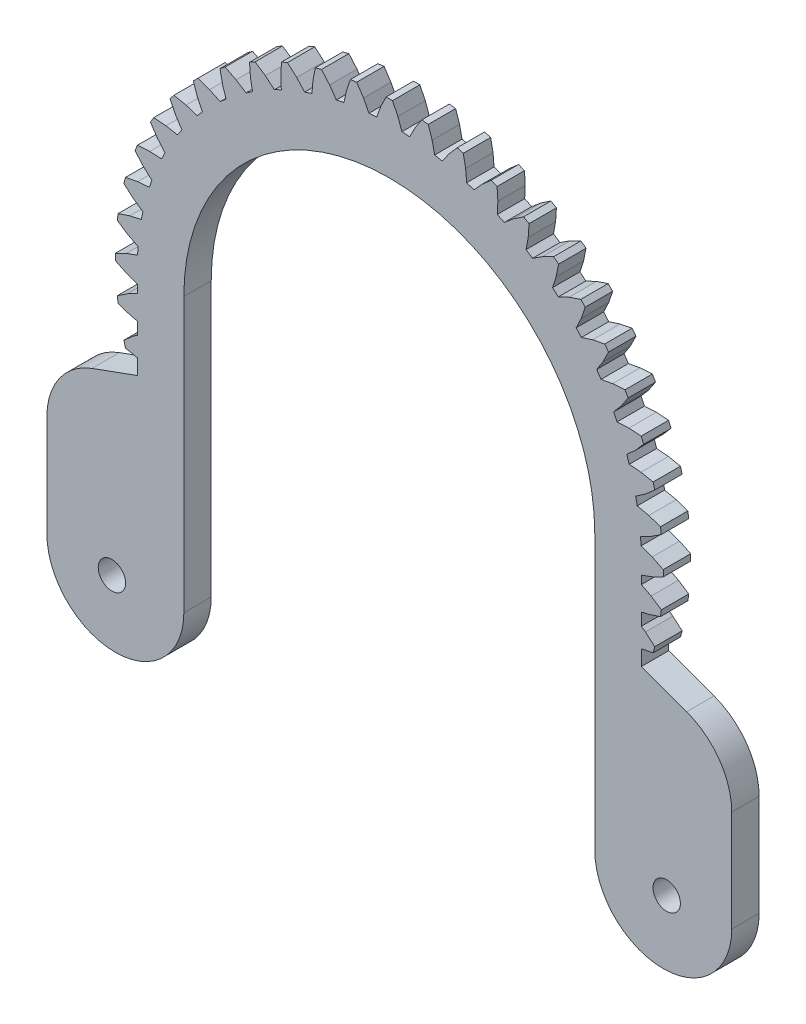
SolidWorks part; units mm, degrees
material "Delrin 2700 NC010, Low Viscosity Acetal Copolymer (SS)"
ref_plane "Front Plane" through (0, 0, 0) normal (0, 0, 1) x (1, 0, 0)
ref_plane "Top Plane" through (0, 0, 0) normal (0, 1, 0) x (1, 0, 0)
ref_plane "Right Plane" through (0, 0, 0) normal (1, 0, 0) x (0, 0, -1)
sketch "Sketch1" plane through (0, 0, 0) normal (0, 0, 1) x (1, 0, 0)
  line L0 (83.8835, 67.191) -> (85.5092, 66.6061)
  line L1 (85.5092, 66.6061) -> (87.1271, 65.8138)
  line L2 (87.1271, 65.8138) -> (87.1271, 64.8854)
  line L3 (87.1271, 64.8854) -> (85.5092, 64.0931)
  line L4 (85.5092, 64.0931) -> (83.8835, 63.5083)
  line L5 (83.8835, 63.5083) -> (83.8095, 62.3776)
  line L6 (83.8095, 62.3776) -> (85.3448, 61.5855)
  line L7 (85.3448, 61.5855) -> (86.8456, 60.5888)
  line L8 (86.8456, 60.5888) -> (86.7243, 59.6683)
  line L9 (86.7243, 59.6683) -> (85.0168, 59.094)
  line L10 (85.0168, 59.094) -> (83.3288, 58.7263)
  line L11 (83.3288, 58.7263) -> (83.1077, 57.615)
  line L12 (83.1077, 57.615) -> (84.5266, 56.6293)
  line L13 (84.5266, 56.6293) -> (85.8844, 55.4453)
  line L14 (85.8844, 55.4453) -> (85.6441, 54.5485)
  line L15 (85.6441, 54.5485) -> (83.8761, 54.202)
  line L16 (83.8761, 54.202) -> (82.1545, 54.0577)
  line L17 (82.1545, 54.0577) -> (81.7903, 52.9848)
  line L18 (81.7903, 52.9848) -> (83.0684, 51.8222)
  line L19 (83.0684, 51.8222) -> (84.26, 50.4711)
  line L20 (84.26, 50.4711) -> (83.9048, 49.6134)
  line L21 (83.9048, 49.6134) -> (82.1066, 49.5006)
  line L22 (82.1066, 49.5006) -> (80.3809, 49.5823)
  line L23 (80.3809, 49.5823) -> (79.8799, 48.5661)
  line L24 (79.8799, 48.5661) -> (80.9952, 47.2468)
  line L25 (80.9952, 47.2468) -> (82.0003, 45.7516)
  line L26 (82.0003, 45.7516) -> (81.5361, 44.9476)
  line L27 (81.5361, 44.9476) -> (79.7387, 45.0704)
  line L28 (79.7387, 45.0704) -> (78.0384, 45.3766)
  line L29 (78.0384, 45.3766) -> (77.4089, 44.4346)
  line L30 (77.4089, 44.4346) -> (78.3426, 42.9809)
  line L31 (78.3426, 42.9809) -> (79.1439, 41.3674)
  line L32 (79.1439, 41.3674) -> (78.5788, 40.6309)
  line L33 (78.5788, 40.6309) -> (76.8128, 40.9873)
  line L34 (76.8128, 40.9873) -> (75.167, 41.5128)
  line L35 (75.167, 41.5128) -> (74.4199, 40.6609)
  line L36 (74.4199, 40.6609) -> (75.1558, 39.0979)
  line L37 (75.1558, 39.0979) -> (75.7397, 37.3936)
  line L38 (75.7397, 37.3936) -> (75.0832, 36.737)
  line L39 (75.0832, 36.737) -> (73.3788, 37.3209)
  line L40 (73.3788, 37.3209) -> (71.8158, 38.0569)
  line L41 (71.8158, 38.0569) -> (70.9639, 37.3097)
  line L42 (70.9639, 37.3097) -> (71.4895, 35.6639)
  line L43 (71.4895, 35.6639) -> (71.8459, 33.898)
  line L44 (71.8459, 33.898) -> (71.1093, 33.3328)
  line L45 (71.1093, 33.3328) -> (69.4958, 34.1341)
  line L46 (69.4958, 34.1341) -> (68.0421, 35.0679)
  line L47 (68.0421, 35.0679) -> (67.1001, 34.4384)
  line L48 (67.1001, 34.4384) -> (67.4064, 32.738)
  line L49 (67.4064, 32.738) -> (67.5292, 30.9407)
  line L50 (67.5292, 30.9407) -> (66.7251, 30.4764)
  line L51 (66.7251, 30.4764) -> (65.23, 31.4815)
  line L52 (65.23, 31.4815) -> (63.9107, 32.5969)
  line L53 (63.9107, 32.5969) -> (62.8945, 32.0958)
  line L54 (62.8945, 32.0958) -> (62.9762, 30.3701)
  line L55 (62.9762, 30.3701) -> (62.8633, 28.572)
  line L56 (62.8633, 28.572) -> (62.0056, 28.2167)
  line L57 (62.0056, 28.2167) -> (60.6545, 29.4083)
  line L58 (60.6545, 29.4083) -> (59.4919, 30.6864)
  line L59 (59.4919, 30.6864) -> (58.419, 30.3222)
  line L60 (58.419, 30.3222) -> (58.2748, 28.6006)
  line L61 (58.2748, 28.6006) -> (57.9283, 26.8327)
  line L62 (57.9283, 26.8327) -> (57.0315, 26.5924)
  line L63 (57.0315, 26.5924) -> (55.8474, 27.9502)
  line L64 (55.8474, 27.9502) -> (54.8618, 29.369)
  line L65 (54.8618, 29.369) -> (53.7504, 29.1479)
  line L66 (53.7504, 29.1479) -> (53.3827, 27.4599)
  line L67 (53.3827, 27.4599) -> (52.8084, 25.7524)
  line L68 (52.8084, 25.7524) -> (51.888, 25.6311)
  line L69 (51.888, 25.6311) -> (50.8913, 27.1319)
  line L70 (50.8913, 27.1319) -> (50.0992, 28.6672)
  line L71 (50.0992, 28.6672) -> (48.9685, 28.5932)
  line L72 (48.9685, 28.5932) -> (48.3836, 26.9675)
  line L73 (48.3836, 26.9675) -> (47.5914, 25.3496)
  line L74 (47.5914, 25.3496) -> (46.6629, 25.3496)
  line L75 (46.6629, 25.3496) -> (45.8707, 26.9675)
  line L76 (45.8707, 26.9675) -> (45.2858, 28.5932)
  line L77 (45.2858, 28.5932) -> (44.1551, 28.6672)
  line L78 (44.1551, 28.6672) -> (43.363, 27.1319)
  line L79 (43.363, 27.1319) -> (42.3663, 25.6311)
  line L80 (42.3663, 25.6311) -> (41.4459, 25.7524)
  line L81 (41.4459, 25.7524) -> (40.8715, 27.4599)
  line L82 (40.8715, 27.4599) -> (40.5038, 29.1479)
  line L83 (40.5038, 29.1479) -> (39.3925, 29.369)
  line L84 (39.3925, 29.369) -> (38.4068, 27.9502)
  line L85 (38.4068, 27.9502) -> (37.2228, 26.5924)
  line L86 (37.2228, 26.5924) -> (36.326, 26.8327)
  line L87 (36.326, 26.8327) -> (35.9795, 28.6006)
  line L88 (35.9795, 28.6006) -> (35.8352, 30.3222)
  line L89 (35.8352, 30.3222) -> (34.7624, 30.6864)
  line L90 (34.7624, 30.6864) -> (33.5998, 29.4083)
  line L91 (33.5998, 29.4083) -> (32.2487, 28.2167)
  line L92 (32.2487, 28.2167) -> (31.3909, 28.572)
  line L93 (31.3909, 28.572) -> (31.2781, 30.3701)
  line L94 (31.2781, 30.3701) -> (31.3598, 32.0958)
  line L95 (31.3598, 32.0958) -> (30.3436, 32.5969)
  line L96 (30.3436, 32.5969) -> (29.0243, 31.4815)
  line L97 (29.0243, 31.4815) -> (27.5292, 30.4764)
  line L98 (27.5292, 30.4764) -> (26.7251, 30.9407)
  line L99 (26.7251, 30.9407) -> (26.8479, 32.738)
  line L100 (26.8479, 32.738) -> (27.1541, 34.4384)
  line L101 (27.1541, 34.4384) -> (26.2121, 35.0679)
  line L102 (26.2121, 35.0679) -> (24.7585, 34.1341)
  line L103 (24.7585, 34.1341) -> (23.1449, 33.3328)
  line L104 (23.1449, 33.3328) -> (22.4084, 33.898)
  line L105 (22.4084, 33.898) -> (22.7648, 35.6639)
  line L106 (22.7648, 35.6639) -> (23.2904, 37.3097)
  line L107 (23.2904, 37.3097) -> (22.4384, 38.0569)
  line L108 (22.4384, 38.0569) -> (20.8754, 37.3209)
  line L109 (20.8754, 37.3209) -> (19.1711, 36.737)
  line L110 (19.1711, 36.737) -> (18.5146, 37.3936)
  line L111 (18.5146, 37.3936) -> (19.0984, 39.0979)
  line L112 (19.0984, 39.0979) -> (19.8344, 40.6609)
  line L113 (19.8344, 40.6609) -> (19.0872, 41.5128)
  line L114 (19.0872, 41.5128) -> (17.4414, 40.9873)
  line L115 (17.4414, 40.9873) -> (15.6755, 40.6309)
  line L116 (15.6755, 40.6309) -> (15.1103, 41.3674)
  line L117 (15.1103, 41.3674) -> (15.9116, 42.9809)
  line L118 (15.9116, 42.9809) -> (16.8454, 44.4346)
  line L119 (16.8454, 44.4346) -> (16.2159, 45.3766)
  line L120 (16.2159, 45.3766) -> (14.5155, 45.0704)
  line L121 (14.5155, 45.0704) -> (12.7182, 44.9476)
  line L122 (12.7182, 44.9476) -> (12.2539, 45.7516)
  line L123 (12.2539, 45.7516) -> (13.2591, 47.2468)
  line L124 (13.2591, 47.2468) -> (14.3744, 48.5661)
  line L125 (14.3744, 48.5661) -> (13.8733, 49.5823)
  line L126 (13.8733, 49.5823) -> (12.1476, 49.5006)
  line L127 (12.1476, 49.5006) -> (10.3495, 49.6134)
  line L128 (10.3495, 49.6134) -> (9.9942, 50.4711)
  line L129 (9.9942, 50.4711) -> (11.1858, 51.8222)
  line L130 (11.1858, 51.8222) -> (12.4639, 52.9848)
  line L131 (12.4639, 52.9848) -> (12.0997, 54.0577)
  line L132 (12.0997, 54.0577) -> (10.3781, 54.202)
  line L133 (10.3781, 54.202) -> (8.6102, 54.5485)
  line L134 (8.6102, 54.5485) -> (8.3699, 55.4453)
  line L135 (8.3699, 55.4453) -> (9.7277, 56.6293)
  line L136 (9.7277, 56.6293) -> (11.1465, 57.615)
  line L137 (11.1465, 57.615) -> (10.9255, 58.7263)
  line L138 (10.9255, 58.7263) -> (9.2374, 59.094)
  line L139 (9.2374, 59.094) -> (7.5299, 59.6683)
  line L140 (7.5299, 59.6683) -> (7.4086, 60.5888)
  line L141 (7.4086, 60.5888) -> (8.9094, 61.5855)
  line L142 (8.9094, 61.5855) -> (10.4448, 62.3776)
  line L143 (10.4448, 62.3776) -> (10.3707, 63.5083)
  line L144 (10.3707, 63.5083) -> (8.745, 64.0931)
  line L145 (8.745, 64.0931) -> (7.1271, 64.8854)
  line L146 (7.1271, 64.8854) -> (7.1271, 65.8138)
  line L147 (7.1271, 65.8138) -> (8.745, 66.6061)
  line L148 (8.745, 66.6061) -> (10.3707, 67.191)
  line L149 (10.3707, 67.191) -> (10.4448, 68.3216)
  line L150 (10.4448, 68.3216) -> (8.9094, 69.1138)
  line L151 (8.9094, 69.1138) -> (7.4086, 70.1105)
  line L152 (7.4086, 70.1105) -> (7.5299, 71.0309)
  line L153 (7.5299, 71.0309) -> (9.2374, 71.6052)
  line L154 (9.2374, 71.6052) -> (10.9255, 71.9729)
  line L155 (10.9255, 71.9729) -> (11.1465, 73.0842)
  line L156 (11.1465, 73.0842) -> (9.7277, 74.0699)
  line L157 (9.7277, 74.0699) -> (8.3699, 75.254)
  line L158 (8.3699, 75.254) -> (8.6102, 76.1508)
  line L159 (8.6102, 76.1508) -> (10.3781, 76.4973)
  line L160 (10.3781, 76.4973) -> (12.0997, 76.6415)
  line L161 (12.0997, 76.6415) -> (12.4639, 77.7144)
  line L162 (12.4639, 77.7144) -> (11.1858, 78.877)
  line L163 (11.1858, 78.877) -> (9.9942, 80.2281)
  line L164 (9.9942, 80.2281) -> (10.3495, 81.0858)
  line L165 (10.3495, 81.0858) -> (12.1476, 81.1987)
  line L166 (12.1476, 81.1987) -> (13.8733, 81.117)
  line L167 (13.8733, 81.117) -> (14.3744, 82.1332)
  line L168 (14.3744, 82.1332) -> (13.2591, 83.4525)
  line L169 (13.2591, 83.4525) -> (12.2539, 84.9476)
  line L170 (12.2539, 84.9476) -> (12.7182, 85.7516)
  line L171 (12.7182, 85.7516) -> (14.5155, 85.6289)
  line L172 (14.5155, 85.6289) -> (16.2159, 85.3226)
  line L173 (16.2159, 85.3226) -> (16.8454, 86.2646)
  line L174 (16.8454, 86.2646) -> (15.9116, 87.7183)
  line L175 (15.9116, 87.7183) -> (15.1103, 89.3318)
  line L176 (15.1103, 89.3318) -> (15.6755, 90.0684)
  line L177 (15.6755, 90.0684) -> (17.4414, 89.712)
  line L178 (17.4414, 89.712) -> (19.0872, 89.1864)
  line L179 (19.0872, 89.1864) -> (19.8344, 90.0383)
  line L180 (19.8344, 90.0383) -> (19.0984, 91.6013)
  line L181 (19.0984, 91.6013) -> (18.5146, 93.3057)
  line L182 (18.5146, 93.3057) -> (19.1711, 93.9622)
  line L183 (19.1711, 93.9622) -> (20.8754, 93.3783)
  line L184 (20.8754, 93.3783) -> (22.4384, 92.6424)
  line L185 (22.4384, 92.6424) -> (23.2904, 93.3895)
  line L186 (23.2904, 93.3895) -> (22.7648, 95.0353)
  line L187 (22.7648, 95.0353) -> (22.4084, 96.8013)
  line L188 (22.4084, 96.8013) -> (23.1449, 97.3664)
  line L189 (23.1449, 97.3664) -> (24.7585, 96.5651)
  line L190 (24.7585, 96.5651) -> (26.2121, 95.6314)
  line L191 (26.2121, 95.6314) -> (27.1541, 96.2609)
  line L192 (27.1541, 96.2609) -> (26.8479, 97.9612)
  line L193 (26.8479, 97.9612) -> (26.7251, 99.7586)
  line L194 (26.7251, 99.7586) -> (27.5292, 100.2228)
  line L195 (27.5292, 100.2228) -> (29.0243, 99.2177)
  line L196 (29.0243, 99.2177) -> (30.3436, 98.1023)
  line L197 (30.3436, 98.1023) -> (31.3598, 98.6034)
  line L198 (31.3598, 98.6034) -> (31.2781, 100.3291)
  line L199 (31.2781, 100.3291) -> (31.3909, 102.1272)
  line L200 (31.3909, 102.1272) -> (32.2487, 102.4825)
  line L201 (32.2487, 102.4825) -> (33.5998, 101.2909)
  line L202 (33.5998, 101.2909) -> (34.7624, 100.0128)
  line L203 (34.7624, 100.0128) -> (35.8352, 100.377)
  line L204 (35.8352, 100.377) -> (35.9795, 102.0986)
  line L205 (35.9795, 102.0986) -> (36.326, 103.8666)
  line L206 (36.326, 103.8666) -> (37.2228, 104.1068)
  line L207 (37.2228, 104.1068) -> (38.4068, 102.7491)
  line L208 (38.4068, 102.7491) -> (39.3925, 101.3302)
  line L209 (39.3925, 101.3302) -> (40.5038, 101.5513)
  line L210 (40.5038, 101.5513) -> (40.8715, 103.2393)
  line L211 (40.8715, 103.2393) -> (41.4459, 104.9468)
  line L212 (41.4459, 104.9468) -> (42.3663, 105.0681)
  line L213 (42.3663, 105.0681) -> (43.363, 103.5673)
  line L214 (43.363, 103.5673) -> (44.1551, 102.032)
  line L215 (44.1551, 102.032) -> (45.2858, 102.106)
  line L216 (45.2858, 102.106) -> (45.8707, 103.7317)
  line L217 (45.8707, 103.7317) -> (46.6629, 105.3496)
  line L218 (46.6629, 105.3496) -> (47.5914, 105.3496)
  line L219 (47.5914, 105.3496) -> (48.3836, 103.7317)
  line L220 (48.3836, 103.7317) -> (48.9685, 102.106)
  line L221 (48.9685, 102.106) -> (50.0992, 102.032)
  line L222 (50.0992, 102.032) -> (50.8913, 103.5673)
  line L223 (50.8913, 103.5673) -> (51.888, 105.0681)
  line L224 (51.888, 105.0681) -> (52.8084, 104.9468)
  line L225 (52.8084, 104.9468) -> (53.3827, 103.2393)
  line L226 (53.3827, 103.2393) -> (53.7504, 101.5513)
  line L227 (53.7504, 101.5513) -> (54.8618, 101.3302)
  line L228 (54.8618, 101.3302) -> (55.8474, 102.7491)
  line L229 (55.8474, 102.7491) -> (57.0315, 104.1068)
  line L230 (57.0315, 104.1068) -> (57.9283, 103.8666)
  line L231 (57.9283, 103.8666) -> (58.2748, 102.0986)
  line L232 (58.2748, 102.0986) -> (58.419, 100.377)
  line L233 (58.419, 100.377) -> (59.4919, 100.0128)
  line L234 (59.4919, 100.0128) -> (60.6545, 101.2909)
  line L235 (60.6545, 101.2909) -> (62.0056, 102.4825)
  line L236 (62.0056, 102.4825) -> (62.8633, 102.1272)
  line L237 (62.8633, 102.1272) -> (62.9762, 100.3291)
  line L238 (62.9762, 100.3291) -> (62.8945, 98.6034)
  line L239 (62.8945, 98.6034) -> (63.9107, 98.1023)
  line L240 (63.9107, 98.1023) -> (65.23, 99.2177)
  line L241 (65.23, 99.2177) -> (66.7251, 100.2228)
  line L242 (66.7251, 100.2228) -> (67.5292, 99.7586)
  line L243 (67.5292, 99.7586) -> (67.4064, 97.9612)
  line L244 (67.4064, 97.9612) -> (67.1001, 96.2609)
  line L245 (67.1001, 96.2609) -> (68.0421, 95.6314)
  line L246 (68.0421, 95.6314) -> (69.4958, 96.5651)
  line L247 (69.4958, 96.5651) -> (71.1093, 97.3664)
  line L248 (71.1093, 97.3664) -> (71.8459, 96.8013)
  line L249 (71.8459, 96.8013) -> (71.4895, 95.0353)
  line L250 (71.4895, 95.0353) -> (70.9639, 93.3895)
  line L251 (70.9639, 93.3895) -> (71.8158, 92.6424)
  line L252 (71.8158, 92.6424) -> (73.3788, 93.3783)
  line L253 (73.3788, 93.3783) -> (75.0832, 93.9622)
  line L254 (75.0832, 93.9622) -> (75.7397, 93.3057)
  line L255 (75.7397, 93.3057) -> (75.1558, 91.6013)
  line L256 (75.1558, 91.6013) -> (74.4199, 90.0383)
  line L257 (74.4199, 90.0383) -> (75.167, 89.1864)
  line L258 (75.167, 89.1864) -> (76.8128, 89.712)
  line L259 (76.8128, 89.712) -> (78.5788, 90.0684)
  line L260 (78.5788, 90.0684) -> (79.1439, 89.3318)
  line L261 (79.1439, 89.3318) -> (78.3426, 87.7183)
  line L262 (78.3426, 87.7183) -> (77.4089, 86.2646)
  line L263 (77.4089, 86.2646) -> (78.0384, 85.3226)
  line L264 (78.0384, 85.3226) -> (79.7387, 85.6289)
  line L265 (79.7387, 85.6289) -> (81.5361, 85.7516)
  line L266 (81.5361, 85.7516) -> (82.0003, 84.9476)
  line L267 (82.0003, 84.9476) -> (80.9952, 83.4525)
  line L268 (80.9952, 83.4525) -> (79.8799, 82.1332)
  line L269 (79.8799, 82.1332) -> (80.3809, 81.117)
  line L270 (80.3809, 81.117) -> (82.1066, 81.1987)
  line L271 (82.1066, 81.1987) -> (83.9048, 81.0858)
  line L272 (83.9048, 81.0858) -> (84.26, 80.2281)
  line L273 (84.26, 80.2281) -> (83.0684, 78.877)
  line L274 (83.0684, 78.877) -> (81.7903, 77.7144)
  line L275 (81.7903, 77.7144) -> (82.1545, 76.6415)
  line L276 (82.1545, 76.6415) -> (83.8761, 76.4973)
  line L277 (83.8761, 76.4973) -> (85.6441, 76.1508)
  line L278 (85.6441, 76.1508) -> (85.8844, 75.254)
  line L279 (85.8844, 75.254) -> (84.5266, 74.0699)
  line L280 (84.5266, 74.0699) -> (83.1077, 73.0842)
  line L281 (83.1077, 73.0842) -> (83.3288, 71.9729)
  line L282 (83.3288, 71.9729) -> (85.0168, 71.6052)
  line L283 (85.0168, 71.6052) -> (86.7243, 71.0309)
  line L284 (86.7243, 71.0309) -> (86.8456, 70.1105)
  line L285 (86.8456, 70.1105) -> (85.3448, 69.1138)
  line L286 (85.3448, 69.1138) -> (83.8095, 68.3216)
  line L287 (83.8095, 68.3216) -> (83.8835, 67.191)
  line L288 (47.1271, 105.3496) -> (47.1271, 25.3496) construction
  line L289 (7.1271, 65.3496) -> (87.1271, 65.3496) construction
  point P292 (47.1271, 65.3496)
sketch "Sketch2" plane through (0, 0, 0) normal (0, 0, 1) x (1, 0, 0)
  line L0 (-2.8729, 47.1511) -> (10.3271, 51.9555)
  line L1 (47.1271, 65.3496) -> (97.1271, 65.3496) construction
  line L2 (47.1271, 65.3496) -> (47.1271, 15.3496) construction
  line L3 (83.9271, 51.9555) -> (47.1271, 65.3496) construction
  line L4 (83.9271, 51.9555) -> (83.9271, 65.3496)
  line L5 (97.1271, 47.1511) -> (97.1271, 15.3496)
  line L6 (47.1271, 65.3496) -> (47.1271, 15.3496) construction
  line L7 (97.1271, 15.3496) -> (-2.8729, 15.3496)
  line L8 (-2.8729, 47.1511) -> (-2.8729, 15.3496)
  line L9 (47.1271, 65.3496) -> (97.1271, 65.3496) construction
  line L10 (7.1271, 65.3496) -> (87.1271, 65.3496) construction
  line L11 (97.1271, 47.1511) -> (83.9271, 51.9555)
  line L14 (10.3271, 51.9555) -> (10.3271, 65.3496)
  line L15 (10.3271, 65.3496) -> (83.9271, 65.3496)
  line L16 (10.3271, 51.9555) -> (47.1271, 65.3496) construction
  dimension "D1" = 100
  dimension "D2" = 50
  dimension "D3" = 20
  dimension "D5" = 36.8
sketch "Sketch3" plane through (0, 0, 0) normal (0, 0, 1) x (1, 0, 0)
  line L0 (6.6271, 24.8496) -> (-2.8729, 24.8496) construction
  line L1 (-2.8729, 47.1511) -> (-2.8729, 15.3496) construction
  line L2 (6.6271, 24.8496) -> (6.6271, 15.3496) construction
  line L3 (97.1271, 15.3496) -> (-2.8729, 15.3496) construction
  line L4 (47.1271, 65.3496) -> (47.1271, 15.3496) construction
  line L5 (7.1271, 65.3496) -> (87.1271, 65.3496) construction
  line L6 (47.1271, 65.3496) -> (97.1271, 65.3496) construction
  circle A0 centre (6.6271, 24.8496) radius 2
  circle A1 centre (87.6271, 24.8496) radius 2
  dimension "D1" = 4
  dimension "D2" = 81
sketch "Sketch4" plane through (0, 0, 0) normal (0, 0, 1) x (1, 0, 0)
  circle A0 centre (47.1271, 65.3496) radius 30
  dimension "D1" = 60
extrude "Boss-Extrude1" add sketch "Sketch1" along normal blind 4
extrude "Boss-Extrude2" add sketch "Sketch2" along normal blind 4
extrude "Cut-Extrude1" cut sketch "Sketch3" along normal up to next
extrude "Cut-Extrude2" cut sketch "Sketch4" along normal up to next
sketch "Sketch5" plane through (0, 0, 0) normal (0, 0, 1) x (1, 0, 0)
  line L0 (77.1271, 65.3496) -> (77.1271, 15.3496)
  line L1 (-2.8729, 15.3496) -> (97.1271, 15.3496) construction
  line L2 (17.1271, 65.3496) -> (17.1271, 15.3496)
  line L3 (17.1271, 15.3496) -> (77.1271, 15.3496)
  line L4 (17.1271, 65.3496) -> (77.1271, 65.3496)
  circle A0 centre (47.1271, 65.3496) radius 30 construction
  dimension "D1" = 60
extrude "Cut-Extrude3" cut sketch "Sketch5" along normal up to next
fillet "Fillet1" radius 10 6 edges at (77.1271, 15.3496, 2) (17.1271, 15.3496, 2) (-2.8729, 15.3496, 2) (-2.8729, 47.1511, 2) (97.1271, 15.3496, 2) (97.1271, 47.1511, 2)
